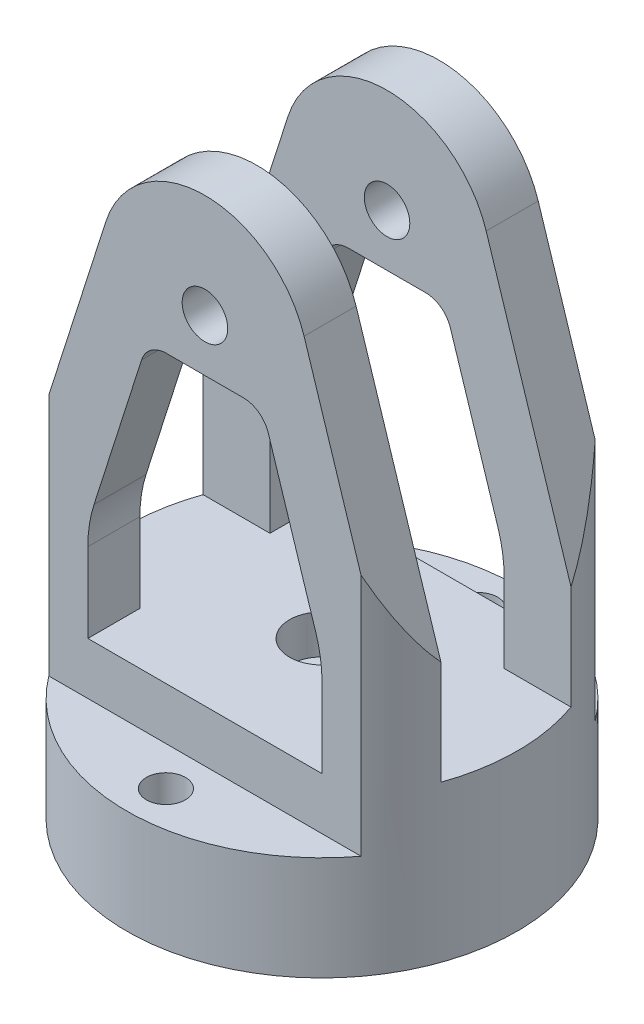
SolidWorks part; units mm, degrees
ref_plane "Front Plane" through (0, 0, 0) normal (0, 0, 1) x (1, 0, 0)
ref_plane "Top Plane" through (0, 0, 0) normal (0, 1, 0) x (1, 0, 0)
ref_plane "Right Plane" through (0, 0, 0) normal (1, 0, 0) x (0, 0, -1)
sketch "Sketch1" plane through (0, 0, 0) normal (1, 0, 0) x (0, 0, -1)
  line L0 (0, 0) -> (47.625, 0)
  line L1 (47.625, 0) -> (47.625, 146.05)
  line L2 (47.625, 146.05) -> (0, 146.05)
  line L3 (0, 0) -> (0, 146.05) construction
  line L4 (0, 38.1) -> (7.9375, 38.1)
  line L5 (7.9375, 38.1) -> (7.9375, 28.575)
  line L6 (7.9375, 28.575) -> (0, 28.575)
  line L7 (0, 0) -> (0, 28.575)
  line L8 (0, 38.1) -> (0, 146.05)
  dimension "D1" = 107.95
  dimension "D2" = 146.05
  dimension "D3" = 9.525
  dimension "D4" = 7.9375
  dimension "D5" = 47.625
revolve "Revolve1" add sketch "Sketch1" angle 360 about L3
sketch "Sketch2" plane through (0, 146.05, 0) normal (0, 1, 0) x (1, 0, 0)
  line L0 (-47.625, 0) -> (47.625, 0) construction
  line L1 (-44.9013, 15.875) -> (44.9013, 15.875)
  line L2 (-38.1, 28.575) -> (38.1, 28.575)
  line L3 (-38.1, -28.575) -> (38.1, -28.575)
  line L4 (-44.9013, -15.875) -> (44.9013, -15.875)
  circle A0 centre (0, 0) radius 47.625 construction
  circle A1 centre (0, 0) radius 47.625
  circle M4 centre (0, 0) radius 47.625
  dimension "D1" = 15.875
  dimension "D2" = 12.7
extrude "Cut-Extrude1" cut sketch "Sketch2" against normal offset from surface (120.65 mm away) 25.4 contours L2 M4 | L3 M4 region at (0, 146.05, -36.3429) region at (0, 146.05, 36.3429) up to face at (0, 0, -47.625)
extrude "Cut-Extrude2" cut sketch "Sketch2<3>" against normal offset from surface (107.95 mm away) 38.1 contours L0 A1 L1 M4 | L0 A1 L4 M4 region at (0, 146.05, -7.8608) region at (0, 146.05, 7.8608) up to face at (0, 0, -47.625)
sketch "Sketch2<3>" plane through (0, 146.05, 0) normal (0, 1, 0) x (1, 0, 0) same geometry as "Sketch2"
sketch "Sketch4" plane through (0, 0, -15.875) normal (0, 0, 1) x (1, 0, 0)
  line L0 (-44.9013, 38.1) -> (-44.9013, 63.5)
  line L1 (-44.9013, 38.1) -> (-44.9013, 146.05) construction
  line L2 (-44.9013, 146.05) -> (44.9013, 146.05) construction
  line L3 (-44.9013, 63.5) -> (-24.1976, 128.3725)
  line L4 (0, 146.05) -> (0, 33.7252) construction
  line L5 (44.9013, 38.1) -> (44.9013, 63.5)
  line L6 (44.9013, 63.5) -> (24.1976, 128.3725)
  line L7 (-44.9013, 63.5) -> (-44.9013, 146.05)
  line L8 (-44.9013, 146.05) -> (44.9013, 146.05)
  line L9 (44.9013, 146.05) -> (44.9013, 63.5)
  line L10 (-9.4125, 107.95) -> (9.4125, 107.95)
  line L11 (-28.575, 38.1) -> (28.575, 38.1)
  line L12 (28.575, 38.1) -> (28.575, 57.4986)
  line L13 (27.072, 67.1518) -> (15.4619, 103.5306)
  line L14 (-28.575, 38.1) -> (-28.575, 57.4986)
  line L15 (-27.072, 67.1518) -> (-15.4619, 103.5306)
  arc A0 (24.1976, 128.3725) -> (-24.1976, 128.3725) centre (0, 120.65) ccw
  circle A1 centre (0, 120.65) radius 5.5562
  arc A2 (27.072, 67.1518) -> (28.575, 57.4986) centre (-3.175, 57.4986) cw
  arc A3 (15.4619, 103.5306) -> (9.4125, 107.95) centre (9.4125, 101.6) ccw
  arc A4 (-15.4619, 103.5306) -> (-9.4125, 107.95) centre (-9.4125, 101.6) cw
  arc A5 (-27.072, 67.1518) -> (-28.575, 57.4986) centre (3.175, 57.4986) ccw
  point P22 (0, 107.95)
  point P36 (0, 38.1)
  line M5 (-44.9013, 38.1) -> (44.9013, 38.1)
  line M6 (44.9013, 38.1) -> (44.9013, 146.05)
  line M7 (44.9013, 146.05) -> (-44.9013, 146.05)
  line M8 (-44.9013, 146.05) -> (-44.9013, 38.1)
  dimension "D2" = 50.8
  dimension "D3" = 11.1125
  dimension "D7" = 31.75
  dimension "D8" = 6.35
  dimension "D1" = 25.4
  dimension "D4" = 12.7
  dimension "D5" = 28.575
  dimension "D6" = 15.875
extrude "Cut-Extrude3" cut sketch "Sketch4" against normal through all and the other way through all contours L4 L10 A4 L15 A5 L14 M5 | L10 L4 L11 L12 A2 L13 A3 | A0 L8 L3 M8 | A0 L6 M6 M7 | L4 A1 | A1 L4 | A1 region at (-34.9848, 119.8572, -15.875) region at (-12.3989, 69.0184, -15.875) region at (12.3989, 69.0184, -15.875) region at (34.9848, 119.8572, -15.875) region at (2.3581, 120.65, -15.875) region at (-2.3581, 120.65, -15.875)
sketch "Sketch5" plane through (0, 25.4, 0) normal (0, 1, 0) x (1, 0, 0)
  line L0 (0, -28.575) -> (0, -38.1) construction
  line L1 (-24.1976, -28.575) -> (24.1976, -28.575) construction
  line L2 (0, -38.1) -> (0, -47.625) construction
  line L3 (0, 0) -> (18.1918, 0) construction
  line L4 (0, 38.1) -> (0, 47.625) construction
  line L5 (0, 28.575) -> (0, 38.1) construction
  circle A0 centre (0, -38.1) radius 4.7625
  arc A1 (-38.1, -28.575) -> (38.1, -28.575) centre (0, 0) ccw construction
  circle A2 centre (0, 38.1) radius 4.7625
  dimension "D1" = 9.525
extrude "Cut-Extrude4" cut sketch "Sketch5" against normal through all
